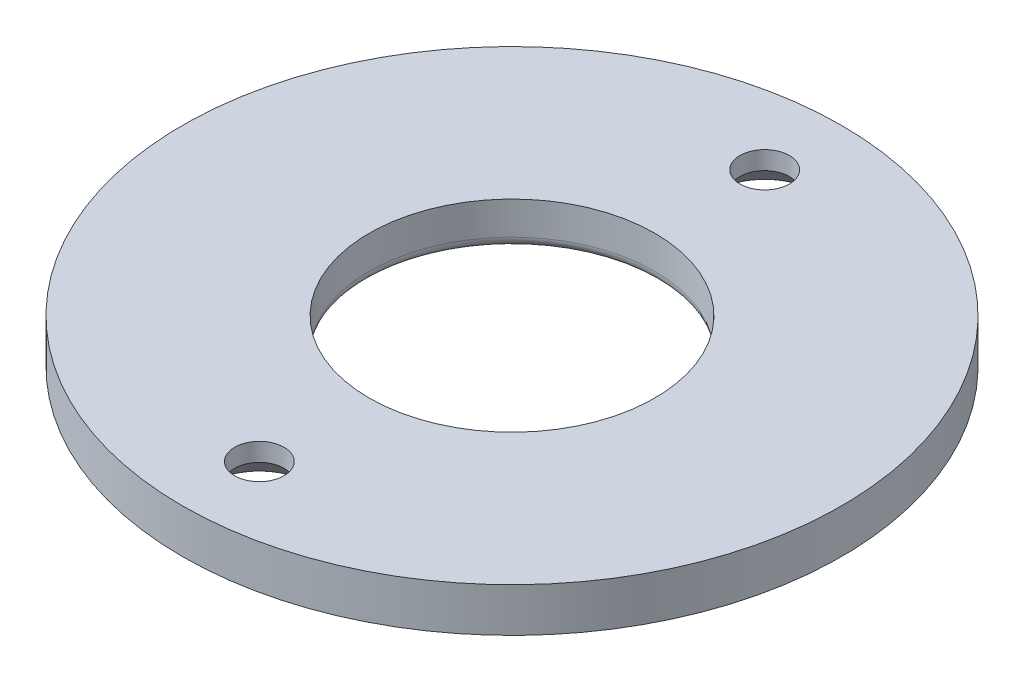
SolidWorks part; units mm, degrees
ref_plane "Front Plane" through (0, 0, 0) normal (0, 0, 1) x (1, 0, 0)
ref_plane "Top Plane" through (0, 0, 0) normal (0, 1, 0) x (1, 0, 0)
ref_plane "Right Plane" through (0, 0, 0) normal (1, 0, 0) x (0, 0, -1)
ref_axis "X" through (88.99, 0, 0) along (-1, 0, 0)
ref_axis "Y" through (0, 55, 0) along (0, -1, 0)
ref_axis "Z" through (0, 0, -88.99) along (0, 0, 1)
sketch "Sketch1" plane through (0, 0, 0) normal (0, 0, 1) x (1, 0, 0)
  line L0 (88.99, 0) -> (-88.99, 0) construction
  line L4 (-30, -2) -> (-30, 2)
  line L5 (-30, 2) -> (-16, 2)
  line L9 (-13, -2) -> (-30, -2)
  line L10 (-13, -2) -> (-13, 4)
  line L13 (-13, 4) -> (-16, 4)
  line L14 (-16, 2) -> (-16, 4)
  point P9 (-30, 0)
  dimension "D1" = 30
  dimension "D2" = 16
  dimension "D3" = 4
  dimension "D4" = 13
  dimension "D6" = 2
revolve "Revolve1" add sketch "Sketch1" angle 360 about axis through (0, 55, 0) along (0, -1, 0)
hole_wizard "CSK for M4 Hex Socket Countersunk Head Screw2" positions "Sketch2" profile "Sketch3" countersink size "M4" standard "DIN" end condition up to next
sketch "Sketch2" plane through (0, -2, 0) normal (0, 1, 0) x (1, 0, 0)
  circle A0 centre (0, 0) radius 23
  point P5 (0, 23)
  point P9 (0, -23)
  dimension "D1" = 46
sketch "Sketch3" plane through (0, -2, 23) normal (1, 0, 0) x (0, 0, -1)
  line L0 (0, 0) -> (0, 4)
  line L1 (0, 4) -> (2.25, 4)
  line L2 (2.25, 4) -> (2.25, 2.34)
  line L3 (2.25, 2.34) -> (4.59, 0)
  line L5 (4.59, 0) -> (0, 0)
  line L6 (-2.25, 2.34) -> (-4.59, 0) construction
  line L11 (0, -6.35) -> (0, 107.95) construction
  dimension "Thru Hole Dia." = 4.5
  dimension "Thru Hole Depth" = 4
  dimension "Near C'Sink Dia." = 9.18
  dimension "Near C'Sink Angle" = 90
sketch "Sketch4" plane through (0, 2, 0) normal (0, 1, 0) x (1, 0, 0)
  line L1 (20, 31.773) -> (-20, 31.773)
  line L2 (20, 31.773) -> (20, -31.5557)
  line L3 (20, -31.5557) -> (-20, -31.5557)
  line L4 (-20, 31.773) -> (-20, -31.5557)
  circle A0 centre (0, 0) radius 16 construction
  dimension "D1" = 20
  dimension "D2" = 20
sketch "Sketch5" plane through (0, -2, 0) normal (0, -1, 0) x (1, 0, 0)
  line L1 (20, 31.5557) -> (40.075, 31.5557)
  line L2 (20, 31.5557) -> (20, -31.773)
  line L3 (20, -31.773) -> (40.075, -31.773)
  line L4 (40.075, 31.5557) -> (40.075, -31.773)
  line L5 (-20, -31.773) -> (-46.6204, -31.773)
  line L6 (-20, -31.773) -> (-20, 31.5557)
  line L7 (-20, 31.5557) -> (-46.6204, 31.5557)
  line L8 (-46.6204, -31.773) -> (-46.6204, 31.5557)
extrude "Cut-Extrude1" [suppressed] cut sketch "Sketch5" against normal blind 10
fillet "Fillet1" radius 1 1 edges at (0, -2, 13)
chamfer "Chamfer1" distance 0.5 angle 45 1 edges at (0, 4, 16)
fillet "Fillet2" [suppressed] radius 1
sketch "Sketch6" plane through (0, 2, 0) normal (0, 1, 0) x (1, 0, 0)
  circle A0 centre (0, 0) radius 20.0745
extrude "Cut-Extrude2" cut sketch "Sketch6" along normal blind 10
